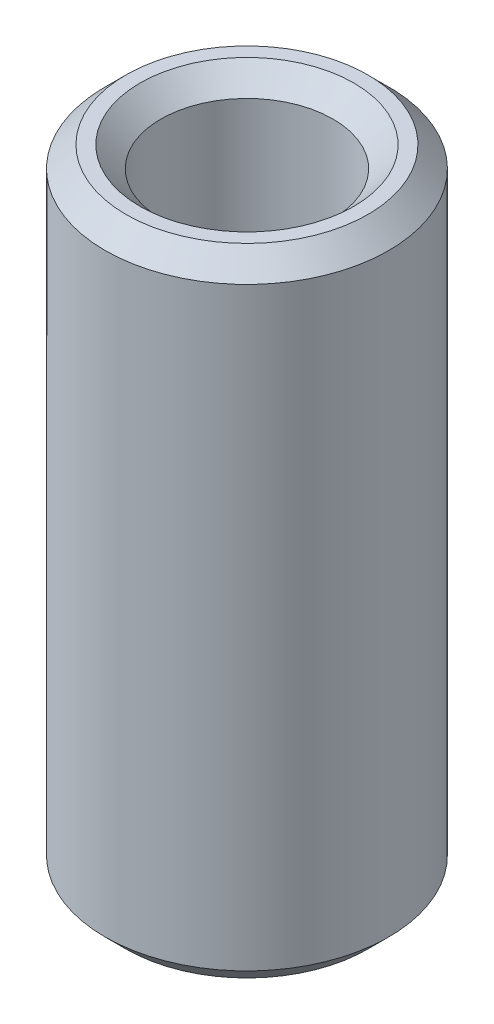
SolidWorks part; units mm, degrees
ref_plane "Front Plane" through (0, 0, 0) normal (0, 0, 1) x (1, 0, 0)
ref_plane "Top Plane" through (0, 0, 0) normal (0, 1, 0) x (1, 0, 0)
ref_plane "Right Plane" through (0, 0, 0) normal (1, 0, 0) x (0, 0, -1)
sketch "Sketch1" plane through (0, 0, 0) normal (0, 1, 0) x (1, 0, 0)
  circle A0 centre (0, 0) radius 20
  dimension "SLEEVE_OD" = 40
extrude "Boss-Extrude1" add sketch "Sketch1" along normal blind 89.7537
sketch "Sketch2" plane through (0, 0, 0) normal (0, 1, 0) x (1, 0, 0)
  circle A0 centre (0, 0) radius 12.146
  dimension "BORE_D" = 24.2919
extrude "Cut-Extrude1" cut sketch "Sketch2" along normal through all
chamfer "Chamfer1" distance 2.9359 angle 45 4 edges at (0, 89.7537, 12.146) (0, 0, 12.146) (0, 0, 20) (0, 89.7537, 20)
